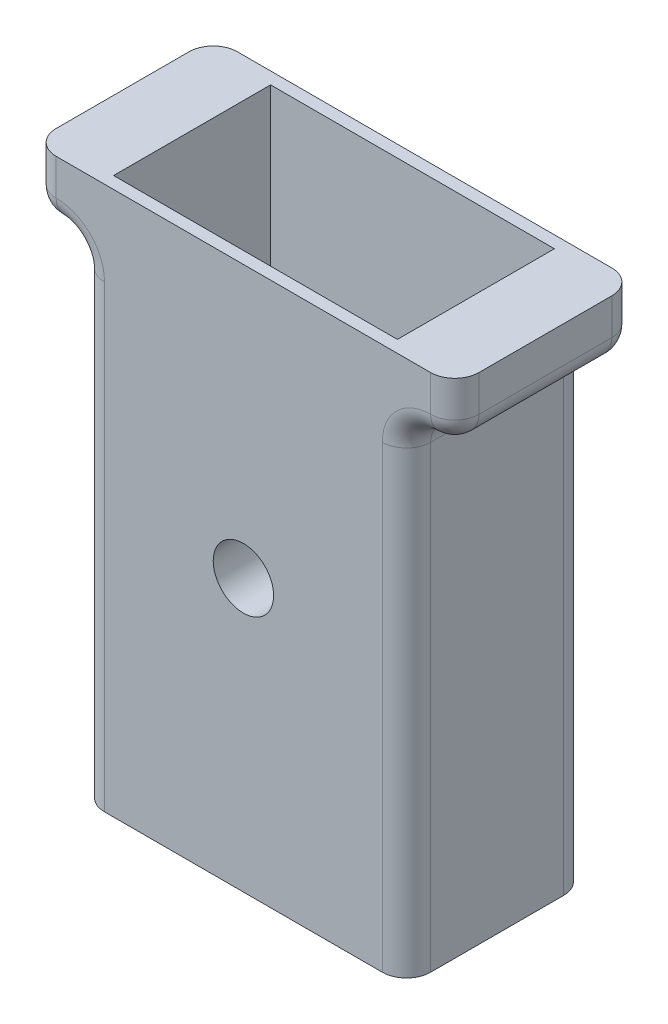
SolidWorks part; units mm, degrees
ref_plane "Front Plane" through (0, 0, 0) normal (0, 0, 1) x (1, 0, 0)
ref_plane "Top Plane" through (0, 0, 0) normal (0, 1, 0) x (1, 0, 0)
ref_plane "Right Plane" through (0, 0, 0) normal (1, 0, 0) x (0, 0, -1)
sketch "Sketch1" plane through (0, 0, 0) normal (0, 1, 0) x (1, 0, 0)
  line L1 (0, 0) -> (27, 0)
  line L2 (0, 0) -> (0, 15)
  line L3 (0, 15) -> (27, 15)
  line L4 (27, 0) -> (27, 15)
  dimension "D1" = 27
  dimension "D2" = 15
extrude "Boss-Extrude1" add sketch "Sketch1" along normal blind 45
sketch "Sketch2" plane through (0, 45, 0) normal (0, 1, 0) x (1, 0, 0)
  line L0 (27, 15) -> (0, 15) construction
  line L1 (-4, 0) -> (31, 0)
  line L2 (-4, 0) -> (-4, 15)
  line L3 (-4, 15) -> (31, 15)
  line L4 (31, 0) -> (31, 15)
  point P6 (13.5, 15)
  point P7 (13.5, 15)
  dimension "D1" = 35
extrude "Boss-Extrude2" add sketch "Sketch2" against normal blind 5
sketch "Sketch3" plane through (0, 45, 0) normal (0, 1, 0) x (1, 0, 0)
  line L0 (-4, 15) -> (-4, 0) construction
  line L1 (1.75, 14) -> (25.25, 14)
  line L2 (1.75, 14) -> (1.75, 1)
  line L3 (1.75, 1) -> (25.25, 1)
  line L4 (25.25, 14) -> (25.25, 1)
  line L5 (31, 15) -> (-4, 15) construction
  point P6 (-4, 7.5)
  point P7 (1.75, 7.5)
  point P10 (13.5, 15)
  point P11 (13.5, 14)
  dimension "D1" = 23.5
  dimension "D2" = 13
extrude "Cut-Extrude1" cut sketch "Sketch3" against normal blind 17
sketch "Sketch4" plane through (0, 0, 0) normal (-1, 0, 0) x (0, 0, 1)
  line L0 (-15, 0) -> (0, 0) construction
  line L1 (-11.75, 31.5) -> (-3.25, 31.5)
  line L2 (-11.75, 31.5) -> (-11.75, 28)
  line L3 (-11.75, 28) -> (-3.25, 28)
  line L4 (-3.25, 31.5) -> (-3.25, 28)
  line L5 (-15, 45) -> (0, 45) construction
  point P6 (-7.5, 0)
  point P7 (-7.5, 28)
  dimension "D1" = 8.5
  dimension "D2" = 3.5
  dimension "D3" = 17
extrude "Cut-Extrude2" cut sketch "Sketch4" against normal blind 17
sketch "Sketch5" plane through (0, 0, -15) normal (0, 0, -1) x (-1, 0, 0)
  line L0 (-27, 0) -> (0, 0) construction
  circle A0 centre (-13.5, 22.5) radius 2.5
  point P2 (0, 0)
  point P5 (-13.5, 0)
  dimension "D1" = 5
  dimension "D2" = 22.5
extrude "Cut-Extrude3" cut sketch "Sketch5" against normal blind 17
fillet "Fillet1" radius 2 12 edges at (-4, 42.5, -15) (-4, 42.5, 0) (-4, 40, -7.5) (0, 40, -7.5) (27, 40, -7.5) (31, 40, -7.5) (31, 42.5, 0) (31, 42.5, -15) (0, 20, -15) (0, 20, 0) (27, 20, 0) (27, 20, -15)
sketch "Sketch6" plane through (0, 0, -15) normal (0, 0, -1) x (-1, 0, 0)
  circle A0 centre (-13.5, 22.5) radius 5.75
  dimension "D1" = 11.5
extrude "Cut-Extrude4" cut sketch "Sketch6" against normal blind 5
